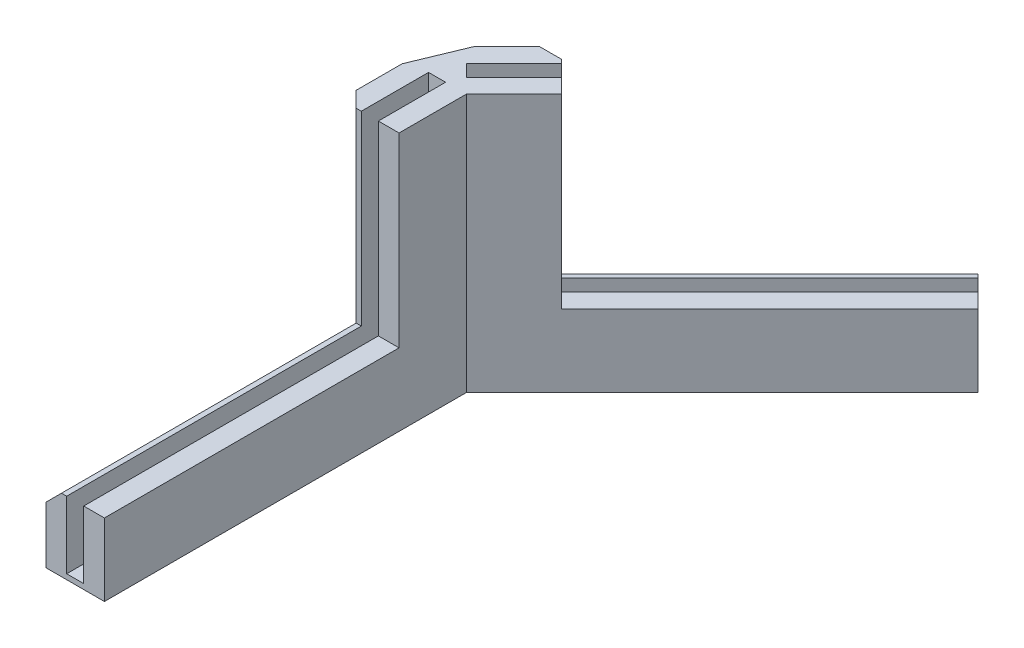
SolidWorks part; units mm, degrees
ref_plane "Front Plane" through (0, 0, 0) normal (0, 0, 1) x (1, 0, 0)
ref_plane "Top Plane" through (0, 0, 0) normal (0, 1, 0) x (1, 0, 0)
ref_plane "Right Plane" through (0, 0, 0) normal (1, 0, 0) x (0, 0, -1)
sketch "Sketch2" plane through (0, 0, 0) normal (0, 1, 0) x (1, 0, 0)
  line L0 (-1.7, -2) -> (-1.7, -15)
  line L1 (-1.7, -15) -> (-5.7, -15)
  line L2 (-5.7, -15) -> (-5.7, -2)
  line L3 (-5.7, -2) -> (-9, -2)
  line L4 (-9, -2) -> (-9, -15)
  line L5 (-9, -15) -> (-13, -15)
  line L7 (-13, -15) -> (-13, 2.6806)
  line L9 (-1.7, -2) -> (-13, 2.6806)
extrude "Boss-Extrude1" add sketch "Sketch2" along normal blind 50
sketch "Sketch3" plane through (0, 0, 2) normal (0, 0, 1) x (1, 0, 0)
  line L0 (-9, 0) -> (-9, 1)
  line L1 (-9, 50) -> (-9, 0) construction
  line L2 (-5.7, 0) -> (-5.7, 1)
  line L3 (-5.7, 50) -> (-5.7, 0) construction
  line L4 (-5.7, 1) -> (-9, 1)
  line L5 (-9, 0) -> (-5.7, 0)
extrude "Boss-Extrude2" add sketch "Sketch3" along normal up to vertex (13 mm away) up to point (-9, 0, 15)
sketch "Sketch5" plane through (0, 0, 15) normal (0, 0, 1) x (1, 0, 0)
  line L0 (-13, 0) -> (-1.7, 0)
  line L1 (-1.7, 50) -> (-1.7, 0) construction
  line L2 (-13, 0) -> (-1.7, 0) construction
  line L3 (-1.7, 0) -> (-1.7, 14)
  line L4 (-13, 0) -> (-13, 14)
  line L5 (-13, 50) -> (-13, 0) construction
  line L6 (-9, 1) -> (-9, 14)
  line L7 (-9, 50) -> (-9, 1) construction
  line L8 (-5.7, 1) -> (-5.7, 14)
  line L9 (-5.7, 50) -> (-5.7, 1) construction
  line L10 (-13, 14) -> (-9, 14)
  line L11 (-9, 1) -> (-5.7, 1)
  line L12 (-5.7, 14) -> (-1.7, 14)
extrude "Boss-Extrude3" add sketch "Sketch5" along normal blind 57
ref_plane "Plane1" through (-0.9561, 0, 2.3081) normal (0.3827, 0, -0.9239) x (-0.9239, 0, -0.3827)
mirror "Mirror1" about plane through (-0.9561, 0, 2.3081) normal (0.3827, 0, -0.9239) of bodies 116 117
fillet "Chamfer1" radius 14 1 edges at (-13, 25, -2.6806) type face fillet profile chamfer first side face at (-13, 21.3333, 28.1065) second side face at (8.7697, 21.3333, -24.4504)
chamfer "Chamfer2" distance 3 angle 45 4 edges at (-13, 32, 15) (-13, 14, 43.5) (19.6546, 14, -35.3353) (-0.4979, 32, -15.1827)
sketch "Sketch6" plane through (0, 50, 0) normal (0, 1, 0) x (1, 0, 0)
  line L0 (-1.7, -2) -> (-10.9498, 1.8314)
  line L1 (-8.8995, 6.7811) -> (-13, -3.1184) construction
